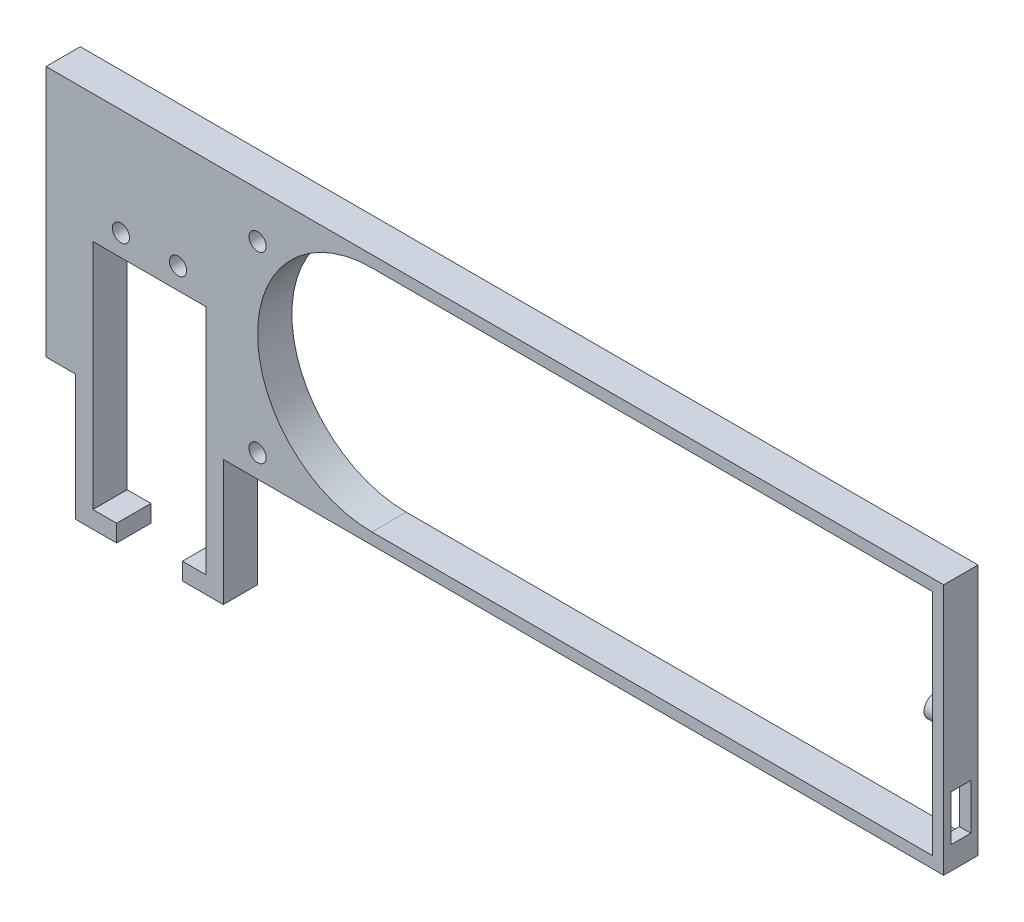
SolidWorks part; units mm, degrees
other "Markup1"
sketch "Sketch3" plane through (63.5, 44, 6) normal (0.035, 0.053, 0.998) x (0.9992, 0.0181, -0.036)
material "ABS"
ref_plane "Front Plane" through (0, 0, 0) normal (0, 0, 1) x (1, 0, 0)
ref_plane "Top Plane" through (0, 0, 0) normal (0, 1, 0) x (1, 0, 0)
ref_plane "Right Plane" through (0, 0, 0) normal (1, 0, 0) x (0, 0, -1)
sketch "Sketch1" plane through (0, 0, 0) normal (0, 0, 1) x (1, 0, 0)
  line L3 (0, 0) -> (100, 0)
  line L4 (100, 0) -> (100, 44)
  line L5 (100, 44) -> (0, 44)
  line L6 (0, 44) -> (-57, 44)
  line L7 (-57, 44) -> (-57, 0)
  line L8 (-57, 0) -> (-51.8, 0)
  line L9 (-51.8, 0) -> (-51.8, -22)
  line L10 (-51.8, -22) -> (-44.65, -22)
  line L11 (-44.65, -22) -> (-44.65, -19)
  line L12 (-44.65, -19) -> (-48.8, -19)
  line L13 (-48.8, -19) -> (-48.8, 21.6)
  line L14 (-48.8, 21.6) -> (-29, 21.6)
  line L15 (-29, 21.6) -> (-29, -19)
  line L16 (-29, -19) -> (-33.15, -19)
  line L17 (-33.15, -19) -> (-33.15, -22)
  line L18 (-33.15, -22) -> (-26, -22)
  line L20 (0, 2) -> (98, 2)
  line L21 (98, 2) -> (98, 42)
  line L22 (98, 42) -> (0, 42)
  line L23 (-43.9, 25.353) -> (-33.9, 25.353) construction
  line L24 (0, 0) -> (-26, 0)
  line L25 (-26, 0) -> (-26, -22)
  line L26 (-44.65, -19) -> (-33.15, -19) construction
  circle A1 centre (-43.9, 25.353) radius 1.5
  circle A2 centre (-33.9, 25.353) radius 1.5
  arc A3 (0, 42) -> (0, 2) centre (0, 22) ccw
  circle A4 centre (-20, 4) radius 1.5
  circle A5 centre (-20, 36) radius 1.5
  point P2 (-38.9, -19)
  point P28 (-38.9, 25.353)
  point P29 (-38.9, 21.6)
  point P30 (-20, 22)
  point P36 (0, 0)
  dimension "D1" = 2
  dimension "D5" = 20
  dimension "D7" = 3
  dimension "D8" = 3
  dimension "D19" = 3
  dimension "D20" = 3
  dimension "D2" = 2
  dimension "D3" = 2
  dimension "D4" = 120
  dimension "D6" = 3.753
  dimension "D9" = 10
  dimension "D10" = 8.2
  dimension "D11" = 40.6
  dimension "D12" = 19.8
  dimension "D13" = 11.5
  dimension "D14" = 3
  dimension "D15" = 3
  dimension "D16" = 3
  dimension "D17" = 22
  dimension "D18" = 37
  dimension "D21" = 8
  dimension "D22" = 4
extrude "Boss-Extrude1" add sketch "Sketch1" along normal blind 6
sketch "Sketch2" plane through (98, 0, 0) normal (-1, 0, 0) x (0, 0, 1)
  line L0 (3, 42) -> (3, 2) construction
  line L1 (6, 42) -> (0, 42) construction
  line L2 (6, 2) -> (0, 2) construction
  circle A0 centre (3, 22) radius 1.905
  point P2 (3, 22)
  dimension "D1" = 3.81
extrude "Boss-Extrude2" add sketch "Sketch2" along normal blind 2.54
sketch "Sketch4" plane through (98, 0, 0) normal (-1, 0, 0) x (0, 0, 1)
  line L0 (1.25, 12) -> (4.75, 12)
  line L1 (4.75, 12) -> (4.75, 4)
  line L2 (4.75, 4) -> (1.25, 4)
  line L3 (1.25, 4) -> (1.25, 12)
  line L4 (0, 2.4647) -> (6, 2.4647) construction
  line L5 (0, 2) -> (0, 42) construction
  line L6 (6, 2) -> (6, 42) construction
  line L7 (6, 2) -> (0, 2) construction
  point P11 (3, 4)
  point P12 (3, 2.4647)
  dimension "D1" = 3.5
  dimension "D2" = 8
  dimension "D3" = 2
extrude "Cut-Extrude1" cut sketch "Sketch4" against normal up to surface (2 mm away) up to face at (100, 22, 3)
